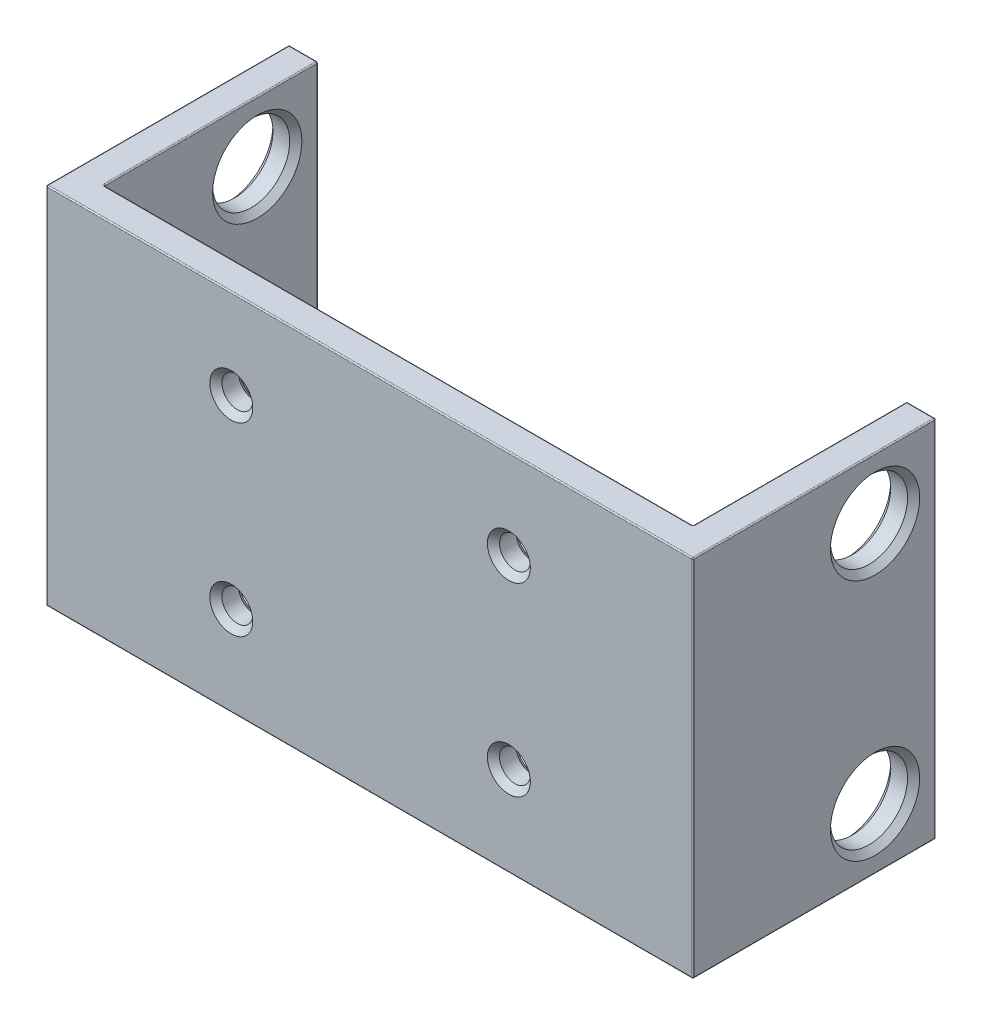
SolidWorks part; units mm, degrees
ref_plane "Front Plane" through (0, 0, 0) normal (0, 0, 1) x (1, 0, 0)
ref_plane "Top Plane" through (0, 0, 0) normal (0, 1, 0) x (1, 0, 0)
ref_plane "Right Plane" through (0, 0, 0) normal (1, 0, 0) x (0, 0, -1)
sketch "Sketch1" plane through (0, 0, 0) normal (0, 1, 0) x (1, 0, 0)
  line L0 (0, 0) -> (0, 17.6188)
  line L1 (0, 17.6188) -> (2.3813, 17.6188)
  line L2 (2.3813, 17.6188) -> (2.3813, -2.3812)
  line L3 (2.3813, -2.3812) -> (-50.8812, -2.3813)
  line L5 (-48.5, 0) -> (0, 0)
  line L6 (-48.5, 0) -> (-48.5, 17.6188)
  line L7 (-48.5, 17.6188) -> (-50.8812, 17.6188)
  line L8 (-50.8812, 17.6188) -> (-50.8812, -2.3813)
  point P4 (-47.6188, -2.5819)
  point P11 (-64.8565, -2.3813)
  dimension "D1" = 2.3813
  dimension "D2" = 20
  dimension "D4" = 2.3813
  dimension "D5" = 20
  dimension "D6" = 48.5
  dimension "D7" = 2.3813
extrude "Boss-Extrude1" add sketch "Sketch1" along normal blind 30
sketch "Sketch2" plane through (0, 0, 2.3812) normal (0, 0, 1) x (1, 0, 0)
  line L4 (-50.8812, 0) -> (2.3813, 0)
  line L5 (2.3813, 0) -> (2.3813, 30)
  line L6 (2.3813, 30) -> (-50.8812, 30)
  line L7 (-50.8812, 30) -> (-50.8812, 0)
  line L8 (-50.8812, 0) -> (2.3813, 0) construction
  line L9 (2.3813, 0) -> (2.3813, 30) construction
  line L10 (2.3813, 30) -> (-50.8812, 30) construction
  line L12 (-50.8812, 30) -> (-50.8812, 0) construction
  circle A0 centre (-35.64, 7.38) radius 1.27 construction
  circle A1 centre (-35.64, 7.38) radius 1.27
  circle A2 centre (-12.78, 7.38) radius 1.27 construction
  circle A3 centre (-12.78, 7.38) radius 1.27
  circle A4 centre (-12.78, 22.62) radius 1.27 construction
  circle A5 centre (-12.78, 22.62) radius 1.27
  circle A6 centre (-35.64, 22.62) radius 1.27 construction
  circle A7 centre (-35.64, 22.62) radius 1.27
  dimension "D1" = 0
extrude "Cut-Extrude1" cut sketch "Sketch2" against normal through all
sketch "Sketch3" plane through (2.3813, 0, 0) normal (1, 0, 0) x (0, 0, -1)
  line L4 (-2.3812, 0) -> (17.6188, 0)
  line L5 (17.6188, 0) -> (17.6188, 30)
  line L6 (17.6188, 30) -> (-2.3812, 30)
  line L7 (-2.3812, 30) -> (-2.3812, 0)
  line L8 (-2.3812, 0) -> (17.6188, 0) construction
  line L9 (17.6188, 0) -> (17.6188, 30) construction
  line L10 (17.6188, 30) -> (-2.3812, 30) construction
  line L11 (-2.3812, 30) -> (-2.3812, 0) construction
  circle A0 centre (12.6188, 25) radius 3.175
  circle A1 centre (12.6188, 5) radius 3.175
  point P2 (12.6188, 25)
  point P4 (12.6188, 5)
  dimension "D5" = 6.35
  dimension "D2" = 20
  dimension "D3" = 5
  dimension "D4" = 15
  dimension "D1" = 0
extrude "Cut-Extrude2" cut sketch "Sketch3" against normal through all
fillet "Fillet1" radius 0.1 24 edges at (-48.5, 15, -17.6188) (-50.8812, 15, -17.6188) (2.3813, 15, -17.6188) (0, 15, -17.6188) (-48.5, 0, -8.8094) (-49.6906, 0, -17.6188) (-50.8812, 0, -7.6188) (-24.25, 0, 2.3813) (2.3813, 0, -7.6188) (1.1906, 0, -17.6188) (0, 0, -8.8094) (-24.25, 0, 0) (0, 30, -8.8094) (1.1906, 30, -17.6188) (2.3813, 30, -7.6188) (-24.25, 30, 2.3813) (-50.8812, 30, -7.6188) (-49.6906, 30, -17.6188) (-48.5, 30, -8.8094) (-24.25, 30, 0) (-50.8812, 15, 2.3813) (2.3813, 15, 2.3812) (0, 15, 0) (-48.5, 15, 0)
chamfer "Chamfer1" distance 0.5 angle 45 16 edges at (0, 5, -15.7938) (2.3813, 5, -15.7938) (0, 25, -15.7938) (2.3813, 25, -15.7938) (-48.5, 25, -9.4437) (-50.8812, 25, -15.7938) (-48.5, 5, -9.4437) (-50.8812, 5, -15.7938) (-11.51, 7.38, 0) (-11.51, 7.38, 2.3812) (-11.51, 22.62, 0) (-11.51, 22.62, 2.3812) (-34.37, 7.38, 0) (-34.37, 7.38, 2.3812) (-34.37, 22.62, 0) (-34.37, 22.62, 2.3812)
